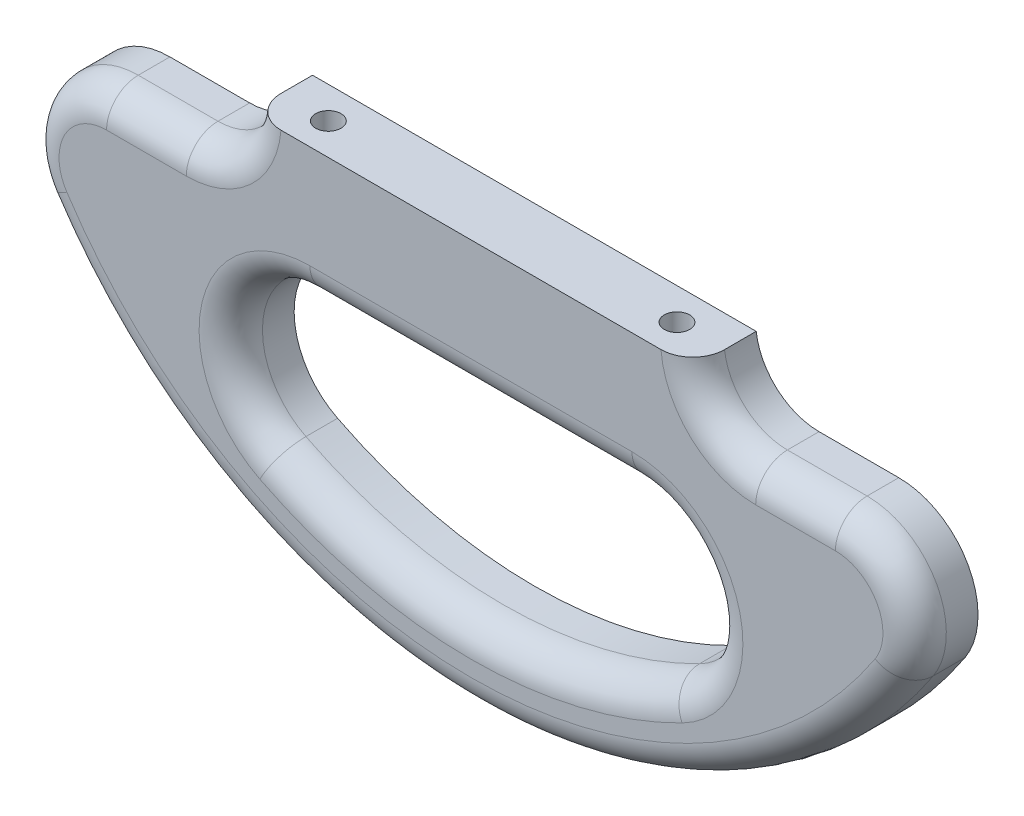
SolidWorks part; units mm, degrees
ref_plane "Front Plane" through (0, 0, 0) normal (0, 0, 1) x (1, 0, 0)
ref_plane "Top Plane" through (0, 0, 0) normal (0, 1, 0) x (1, 0, 0)
ref_plane "Right Plane" through (0, 0, 0) normal (1, 0, 0) x (0, 0, -1)
sketch "Sketch1" plane through (0, 0, 0) normal (0, 0, 1) x (1, 0, 0)
  line L0 (55, 0) -> (-55, 0) construction
  line L1 (-46, 0) -> (46, 0) construction
  line L2 (-46, 10) -> (46, 10)
  line L3 (-46, -10) -> (46, -10)
  circle A0 centre (-46, 0) radius 2.15
  circle A1 centre (46, 0) radius 2.15
  arc A2 (-46, 10) -> (-46, -10) centre (-46, 0) ccw
  arc A3 (46, -10) -> (46, 10) centre (46, 0) ccw
  dimension "D2" = 4.3
  dimension "D1" = 92
  dimension "D3" = 10
extrude "Boss-Extrude1" add sketch "Sketch1" along normal blind 8
sketch "Sketch2" plane through (0, 0, 8) normal (0, 0, 1) x (1, 0, 0)
  line L2 (-46, -10) -> (46, -10)
  line L3 (46, 10) -> (-46, 10)
  line L4 (-46, -10) -> (46, -10)
  line L5 (46, 10) -> (-46, 10)
  arc A2 (-46, 10) -> (-46, -10) centre (-46, 0) ccw
  arc A3 (46, -10) -> (46, 10) centre (46, 0) ccw
  arc A4 (-46, 10) -> (-46, -10) centre (-46, 0) ccw
  arc A5 (46, -10) -> (46, 10) centre (46, 0) ccw
  dimension "D1" = 0
extrude "Boss-Extrude2" add sketch "Sketch2" against normal blind 4
sketch "Sketch3" plane through (0, 10, 0) normal (0, 1, 0) x (1, 0, 0)
  line L0 (-28, 0) -> (-28, -8)
  line L1 (46, 0) -> (-46, 0) construction
  line L3 (-28, -8) -> (28, -8)
  line L4 (28, -8) -> (28, 0)
  line L5 (28, 0) -> (-28, 0)
  line L6 (46, -8) -> (-46, -8) construction
  point P6 (0, 0)
  dimension "D1" = 56
extrude "Boss-Extrude6" add sketch "Sketch3" along normal blind 7
sketch "Sketch4" plane through (0, 0, 8) normal (0, 0, 1) x (1, 0, 0)
  line L3 (-46, -10) -> (46, -10) construction
  line L4 (-46, -10) -> (46, -10)
  arc A5 (46, -10) -> (46, 10) centre (46, 0) ccw construction
  arc A6 (-46, 10) -> (-46, -10) centre (-46, 0) ccw construction
  arc A7 (46, -10) -> (54.3636, -5.4818) centre (46, 0) ccw
  arc A8 (-54.3636, -5.4818) -> (-46, -10) centre (-46, 0) ccw
  arc A9 (-54.3636, -5.4818) -> (54.3636, -5.4818) centre (0, 30.1496) ccw
  dimension "D1" = 65
extrude "Boss-Extrude4" add sketch "Sketch4" against normal up to surface (8 mm away) up to face at (0, 6.75, 0)
sketch "Sketch5" plane through (0, 0, 0) normal (0, 0, -1) x (-1, 0, 0)
  line L6 (-20.3226, 0) -> (20.3226, 0)
  line L14 (-46, 10) -> (-28, 10) construction
  arc A10 (20.3226, 0) -> (24.8387, -18.9221) centre (20.3226, -10) cw
  arc A11 (-20.3226, 0) -> (-24.8387, -18.9221) centre (-20.3226, -10) ccw
  arc A14 (-24.8387, -18.9221) -> (24.8387, -18.9221) centre (0, 30.1496) ccw
  arc A16 (-54.3636, -5.4818) -> (54.3636, -5.4818) centre (0, 30.1496) ccw construction
  dimension "D2" = 10
  dimension "D1" = 10
  dimension "D3" = 10
extrude "Cut-Extrude1" cut sketch "Sketch5" against normal through all
fillet "Fillet4" radius 8 2 edges at (28, 10, 4) (-28, 10, 4)
fillet "Fillet3" radius 4 11 edges at (30.0494, -7.6785, 8) (0, 0, 8) (-30.0494, -7.6785, 8) (0, -24.8504, 8) (40.9686, 10, 8) (54.7982, 4.753, 8) (0, -34.8504, 8) (-54.7982, 4.753, 8) (-40.9686, 10, 8) (-30.6458, 12, 8) (30.6458, 12, 8)
hole_wizard "M3 Clearance Hole1" positions "Sketch6" profile "Sketch7" hole size "M3" standard "ANSI Metric"
sketch "Sketch6" plane through (0, 17, 0) normal (0, 1, 0) x (1, 0, 0)
  line L0 (28, 0) -> (-28, 0) construction
  line L1 (28, -4) -> (28, 0) construction
  point P0 (-22, -4)
  point P2 (22, -4)
  dimension "D1" = 44
  dimension "D2" = 4
  dimension "D3" = 4
  dimension "6" = 6
sketch "Sketch7" plane through (-22, 17, 4) normal (1, 0, 0) x (0, 0, 1)
  line L0 (0, 0) -> (0, 8.9614)
  line L1 (0, 8.9614) -> (1.6, 8)
  line L2 (1.6, 8) -> (1.6, 0)
  line L5 (1.6, 0) -> (0, 0)
  line L10 (0, 8.9614) -> (-1.6, 8) construction
  line L11 (0, -6.35) -> (0, 107.95) construction
  dimension "Hole Dia." = 3.2
  dimension "Hole Depth" = 8
  dimension "Drill Angle" = 118
